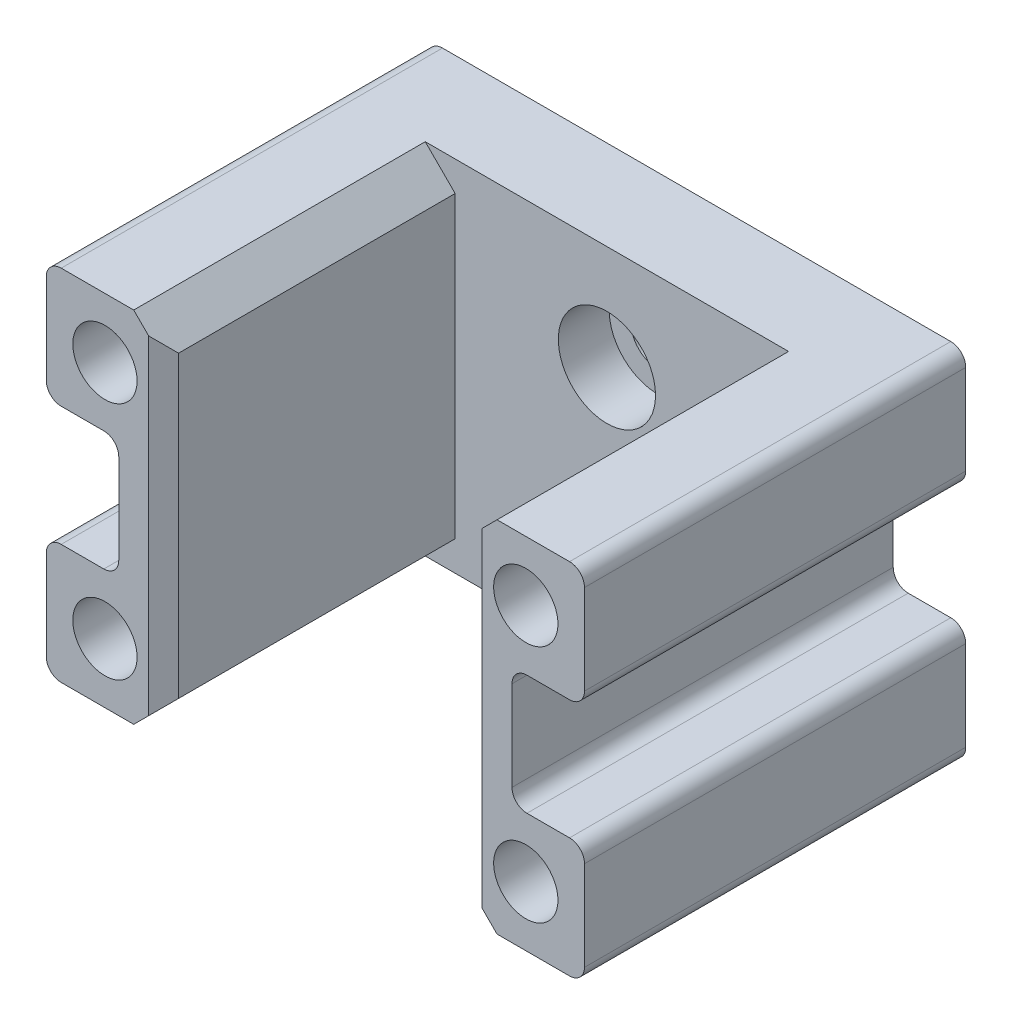
SolidWorks part; units mm, degrees
ref_plane "Płaszczyzna przednia" through (0, 0, 0) normal (0, 0, 1) x (1, 0, 0)
ref_plane "Płaszczyzna górna" through (0, 0, 0) normal (0, 1, 0) x (1, 0, 0)
ref_plane "Płaszczyzna prawa" through (0, 0, 0) normal (1, 0, 0) x (0, 0, -1)
sketch "Sketch1" plane through (0, 0, 0) normal (0, 0, 1) x (1, 0, 0)
  line L1 (0, 0) -> (36, 0)
  line L2 (0, 0) -> (0, 24)
  line L3 (0, 24) -> (36, 24)
  line L4 (36, 0) -> (36, 24)
  dimension "D1" = 24
  dimension "D2" = 36
extrude "Boss-Extrude1" add sketch "Sketch1" along normal blind 6
hole_wizard "CBORE for M3 Hex Socket Head Cap Screw1" positions "Sketch2" profile "Sketch3" counterbore size "M3" standard "DIN"
sketch "Sketch2" plane through (0, 0, 6) normal (0, 0, 1) x (1, 0, 0)
  line L0 (18, 0) -> (18, 7) construction
  line L1 (0, 0) -> (36, 0) construction
  line L2 (18, 7) -> (18, 17) construction
  line L4 (18, 17) -> (18, 24) construction
  line L5 (36, 24) -> (0, 24) construction
  point P0 (18, 17)
  point P2 (18, 7)
  dimension "D1" = 10
sketch "Sketch3" plane through (18, 17, 6) normal (1, 0, 0) x (0, -1, 0)
  line L0 (0, 0) -> (0, 13.0815)
  line L1 (0, 13.0815) -> (1.8, 12)
  line L2 (1.8, 12) -> (1.8, 3.4)
  line L3 (1.8, 3.4) -> (3.25, 3.4)
  line L4 (3.25, 3.4) -> (3.25, 0)
  line L5 (3.25, 0) -> (0, 0)
  line L10 (0, 13.0815) -> (-1.8, 12) construction
  line L11 (0, -6.35) -> (0, 107.95) construction
  dimension "Hole Dia." = 3.6
  dimension "Hole Depth" = 12
  dimension "C'Bore Dia." = 6.5
  dimension "C'Bore Depth" = 3.4
  dimension "Drill Angle" = 118
sketch "Sketch4" plane through (0, 0, 6) normal (0, 0, 1) x (1, 0, 0)
  line L0 (0, 0) -> (36, 0) construction
  line L1 (0, 24) -> (7.85, 24)
  line L2 (0, 24) -> (0, 16)
  line L3 (0, 0) -> (7.85, 0)
  line L10 (0, 8) -> (0, 0)
  line L11 (0, 24) -> (7.85, 24)
  line L12 (0, 24) -> (0, 16)
  line L13 (0, 16) -> (4.85, 16)
  line L18 (4.85, 16) -> (4.85, 8)
  line L19 (7.85, 0) -> (0, 0)
  line L21 (4.85, 8) -> (0, 8)
  line L22 (0, 0) -> (0, 8)
  line L23 (7.85, 0) -> (7.85, 24)
  line L24 (18, 17) -> (18, 7) construction
  line L25 (36, 0) -> (28.15, 0)
  line L26 (36, 8) -> (36, 0)
  line L27 (31.15, 8) -> (36, 8)
  line L28 (31.15, 16) -> (31.15, 8)
  line L29 (36, 16) -> (31.15, 16)
  line L30 (36, 24) -> (36, 16)
  line L31 (36, 24) -> (28.15, 24)
  line L32 (28.15, 0) -> (28.15, 24)
  line M8 (0, 24) -> (0, 0)
  line M9 (0, 0) -> (36, 0)
  line M10 (36, 0) -> (36, 24)
  line M11 (36, 24) -> (0, 24)
  dimension "D1" = 7.85
  dimension "D2" = 8
extrude "Boss-Extrude2" add sketch "Sketch4" along normal blind 19.5 contours L23 L13 L18 L21 M9 M11 M8 | L32 L27 L28 L29 M9 M10 M11 region at (3.925, 23.7475, 6) region at (32.075, 23.7475, 6)
sketch "Sketch5" plane through (0, 0, 6) normal (0, 0, 1) x (1, 0, 0)
  line L0 (31.15, 16) -> (31.15, 8) construction
  line L1 (31.15, 8) -> (36, 8) construction
  line L2 (36, 8) -> (36, 16) construction
  line L3 (36, 16) -> (31.15, 16) construction
  line L4 (0, 8) -> (4.85, 8) construction
  line L5 (4.85, 8) -> (4.85, 16) construction
  line L6 (4.85, 16) -> (0, 16) construction
  line L7 (0, 16) -> (0, 8) construction
  line L8 (31.15, 16) -> (31.15, 8)
  line L9 (31.15, 8) -> (36, 8)
  line L10 (36, 8) -> (36, 16)
  line L11 (36, 16) -> (31.15, 16)
  line L12 (0, 8) -> (4.85, 8)
  line L13 (4.85, 8) -> (4.85, 16)
  line L14 (4.85, 16) -> (0, 16)
  line L15 (0, 16) -> (0, 8)
extrude "Cut-Extrude1" cut sketch "Sketch5" against normal through all
hole_wizard "Ø4.3 (4.3) Diameter Hole1" positions "Sketch8" profile "Sketch9" hole size "Ø4.3" standard "DIN"
sketch "Sketch8" plane through (0, 0, 25.5) normal (0, 0, 1) x (1, 0, 0)
  line L0 (0, 4) -> (3.925, 4) construction
  line L1 (0, 8) -> (0, 0) construction
  line L3 (0, 20) -> (3.925, 20) construction
  line L4 (0, 24) -> (0, 16) construction
  line L6 (3.925, 24) -> (3.925, 20) construction
  line L7 (7.85, 24) -> (0, 24) construction
  line L9 (3.925, 4) -> (3.925, 20) construction
  line L11 (18, 17) -> (18, 7) construction
  point P0 (3.925, 20)
  point P2 (3.925, 4)
  point P34 (32.075, 4)
  point P35 (32.075, 20)
sketch "Sketch9" plane through (3.925, 20, 25.5) normal (1, 0, 0) x (0, -1, 0)
  line L0 (0, 0) -> (0, 17.2919)
  line L1 (0, 17.2919) -> (2.15, 16)
  line L2 (2.15, 16) -> (2.15, 0)
  line L5 (2.15, 0) -> (0, 0)
  line L10 (0, 17.2919) -> (-2.15, 16) construction
  line L11 (0, -6.35) -> (0, 107.95) construction
  dimension "Hole Dia." = 4.3
  dimension "Hole Depth" = 16
  dimension "Drill Angle" = 118
fillet "Fillet1" radius 1 12 edges at (31.15, 8, 12.75) (31.15, 16, 12.75) (36, 24, 12.75) (36, 8, 12.75) (36, 16, 12.75) (36, 0, 12.75) (4.85, 16, 12.75) (0, 16, 12.75) (4.85, 8, 12.75) (0, 8, 12.75) (0, 0, 12.75) (0, 24, 12.75)
chamfer "Chamfer1" distance 2 angle 45 4 edges at (28.15, 0, 15.75) (7.85, 0, 15.75) (28.15, 24, 15.75) (7.85, 24, 15.75)
chamfer "Chamfer2" distance 1 angle 45 2 edges at (28.15, 12, 25.5) (7.85, 12, 25.5)
